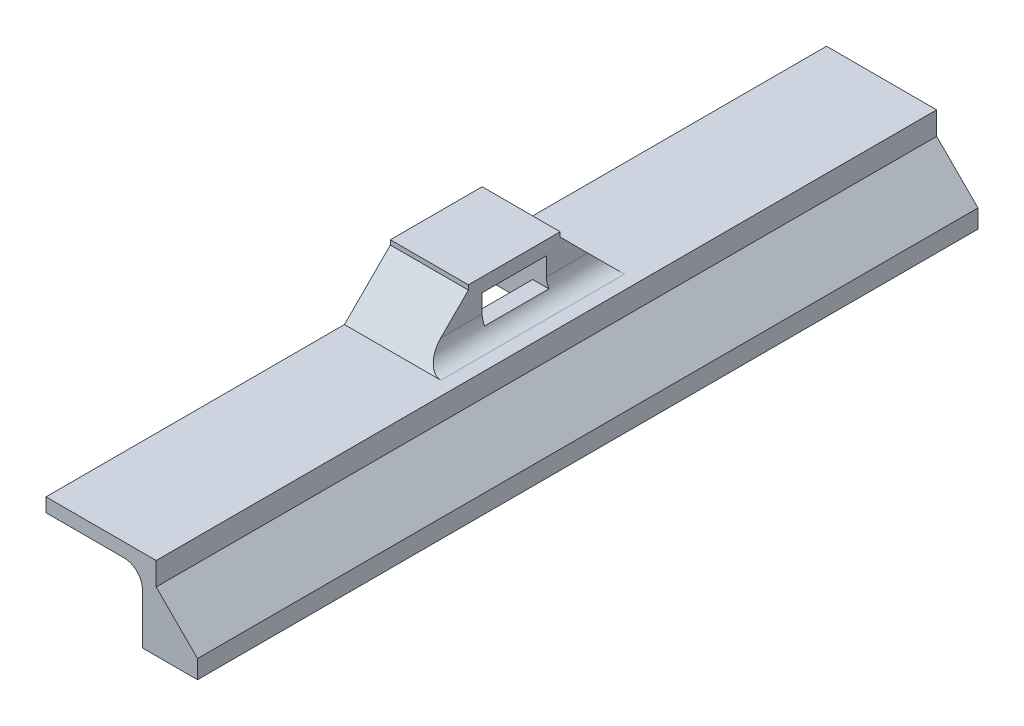
SolidWorks part; units mm, degrees
ref_plane "Спереди" through (0, 0, 0) normal (0, 0, 1) x (1, 0, 0)
ref_plane "Сверху" through (0, 0, 0) normal (0, 1, 0) x (1, 0, 0)
ref_plane "Справа" through (0, 0, 0) normal (1, 0, 0) x (0, 0, -1)
sketch "Эскиз1" plane through (0, 0, 0) normal (0, 1, 0) x (1, 0, 0)
  line L1 (3, -42.5) -> (-3, -42.5)
  line L2 (3, -42.5) -> (3, 42.5)
  line L3 (3, 42.5) -> (-3, 42.5)
  line L4 (-3, -42.5) -> (-3, 42.5)
  line L5 (3, -42.5) -> (-3, 42.5) construction
  line L6 (3, 42.5) -> (-3, -42.5) construction
  point P0 (0, 0)
  dimension "D1" = 6
  dimension "D2" = 85
extrude "Бобышка-Вытянуть1" add sketch "Эскиз1" along normal blind 1.5
sketch "Эскиз2" plane through (0, 1.5, 0) normal (0, 1, 0) x (1, 0, 0)
  line L0 (3, 42.5) -> (-3, 42.5) construction
  line L1 (-3, -42.5) -> (-1.5, -42.5)
  line L2 (-3, -42.5) -> (-3, 42.5)
  line L3 (-3, 42.5) -> (-1.5, 42.5)
  line L4 (-1.5, -42.5) -> (-1.5, 42.5)
  dimension "D1" = 1.5
extrude "Бобышка-Вытянуть2" add sketch "Эскиз2" along normal blind 6
sketch "Эскиз3" plane through (0, 7.5, 0) normal (0, 1, 0) x (1, 0, 0)
  line L0 (-3, 42.5) -> (-3, -42.5) construction
  line L1 (-1.5, -42.5) -> (-13.5, -42.5)
  line L2 (-1.5, -42.5) -> (-1.5, 42.5)
  line L3 (-1.5, 42.5) -> (-13.5, 42.5)
  line L4 (-13.5, -42.5) -> (-13.5, -3.5)
  line L5 (-13.5, 3.5) -> (-13.5, 42.5)
  line L6 (-13.5, 3.5) -> (-6.5, 3.5)
  line L8 (-13.5, -3.5) -> (-6.5, -3.5)
  line L9 (-6.5, 3.5) -> (-6.5, -3.5)
  line L10 (-13.5, 3.5) -> (-6.5, -3.5) construction
  line L11 (-13.5, -3.5) -> (-6.5, 3.5) construction
  point P5 (-13.5, 0)
  point P6 (-10, 0)
  point P7 (-3, 0)
  point P10 (-10, 0)
  dimension "D1" = 12
  dimension "D2" = 7
  dimension "D3" = 7
  dimension "D4" = 7
extrude "Бобышка-Вытянуть3" add sketch "Эскиз3" along normal blind 1.5
sketch "Эскиз4" plane through (0, 9, 0) normal (0, 1, 0) x (1, 0, 0)
  line L0 (-13.5, 3.5) -> (-6.5, 3.5) construction
  line L1 (-13.5, -6.4546) -> (-13.5, 5)
  line L2 (-13.5, 5) -> (-5, 5)
  line L4 (-13.5, -5) -> (-5, -5)
  line L5 (-5, 5) -> (-5, -5)
  line L6 (-13.5, 3.5) -> (-5, -5) construction
  line L7 (-13.5, -3.5) -> (-5, 5) construction
  line L8 (-13.5, -3.5) -> (-13.5, -42.5) construction
  line L9 (-13.5, 42.5) -> (-13.5, 3.5) construction
  point P0 (-10, 3.5)
  point P1 (-10, 0)
  line M5 (-13.5, 42.5) -> (-13.5, 3.5)
  line M6 (-13.5, 3.5) -> (-6.5, 3.5)
  line M7 (-6.5, 3.5) -> (-6.5, -3.5)
  line M8 (-6.5, -3.5) -> (-13.5, -3.5)
  line M9 (-13.5, -3.5) -> (-13.5, -42.5)
  dimension "D1" = 10
  dimension "D3" = 0
  dimension "D4" = 0
extrude "Бобышка-Вытянуть4" add sketch "Эскиз4" along normal blind 5.5 contours L5 L2 L4 M5 M6 M7 M8 M9 | L1 M8 M7 M6 region at (-13.3688, 9, 4.25) region at (-10, 9, 0)
sketch "Эскиз5" plane through (0, 9, 0) normal (0, -1, 0) x (1, 0, 0)
  line L1 (-13.5, 3.5) -> (-6.5, 3.5)
  line L2 (-13.5, 3.5) -> (-13.5, -3.5)
  line L3 (-13.5, -3.5) -> (-6.5, -3.5)
  line L4 (-6.5, 3.5) -> (-6.5, -3.5)
extrude "Вырез-Вытянуть1" cut sketch "Эскиз5" against normal blind 4
sketch "Эскиз6" plane through (-5, 0, 0) normal (1, 0, 0) x (0, 0, -1)
  line L0 (-5, 14.5) -> (-5, 9) construction
  line L1 (5, 14.5) -> (-5, 14.5) construction
  line L2 (5, 14.5) -> (5, 9) construction
  line L3 (-3.5, 10) -> (3.5, 10)
  line L4 (-3.5, 10) -> (-3.5, 13)
  line L5 (-3.5, 13) -> (3.5, 13)
  line L6 (3.5, 10) -> (3.5, 13)
  point P0 (-3.5, 13)
  point P5 (-3.5, 10)
  dimension "D1" = 1.5
  dimension "D2" = 1.5
  dimension "D3" = 3
  dimension "D4" = 1.5
extrude "Вырез-Вытянуть2" cut sketch "Эскиз6" against normal blind 4
chamfer "Фаска1" distance 5 angle 45 1 edges
chamfer "Фаска2" distance 5 angle 45 2 edges
fillet "Скругление1" radius 2 1 edges at (-5, 9, 0)
fillet "Скругление2" radius 2 1 edges
